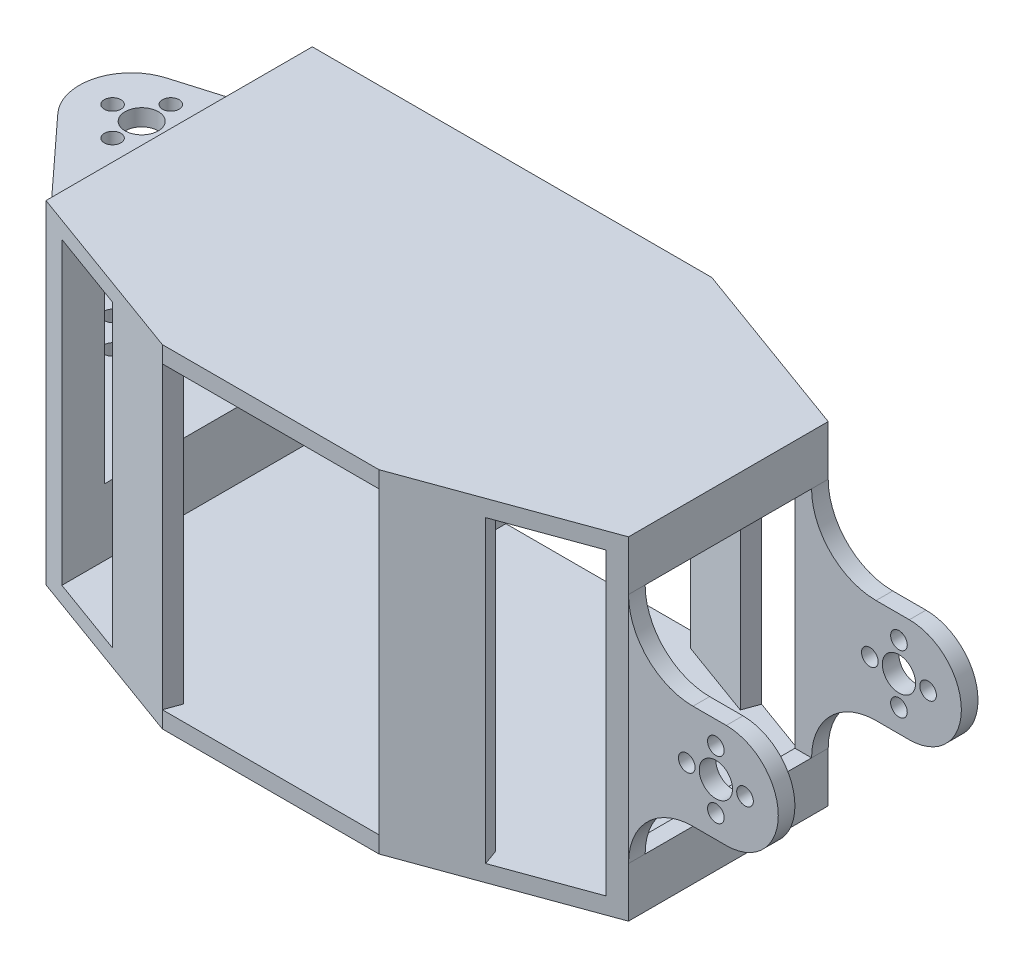
SolidWorks part; units mm, degrees
ref_plane "Alzado" through (0, 0, 0) normal (1, 0, 0) x (0, 1, 0)
ref_plane "Planta" through (0, 0, 0) normal (0, 0, 1) x (0, 1, 0)
ref_plane "Vista lateral" through (0, 0, 0) normal (0, 1, 0) x (-1, 0, 0)
sketch "Croquis2" plane through (0, 0, 0) normal (0, 0, 1) x (0, 1, 0)
  line L1 (-24, 29.7419) -> (24, 29.7419)
  line L2 (-24, 29.7419) -> (-24, -6.2581)
  line L3 (-24, -6.2581) -> (24, -6.2581)
  line L4 (24, 29.7419) -> (24, -6.2581)
  line L5 (-20, 30.4769) -> (20, 30.4769)
  line L6 (-20, 30.4769) -> (-20, -4.2581)
  line L7 (-20, -4.2581) -> (20, -4.2581)
  line L8 (20, 30.4769) -> (20, -4.2581)
  point P8 (0, 29.7419)
  point P9 (0, 30.4769)
  dimension "D1" = 4
  dimension "D2" = 4
  dimension "D3" = 2
  dimension "D4" = 40
  dimension "D5" = 36
  dimension "D6" = 48
extrude "Saliente-Extruir1" add sketch "Croquis2" along normal blind 25 contours L1 L8 L7 L6 L2 L3 L4 region at (-29.1419, -22, 0)
sketch "Croquis3" plane through (0, 24, 0) normal (0, 1, 0) x (-1, 0, 0)
  line L2 (29.7419, 0) -> (-6.2581, 0) construction
  line L3 (29.7419, 12.5) -> (-6.2581, 12.5) construction
  line L4 (29.7419, 25) -> (29.7419, 0) construction
  line L5 (-6.2581, 25) -> (-6.2581, 0) construction
  circle A0 centre (14.7419, 12.5) radius 4
  circle A1 centre (14.7419, 19.5) radius 2
  circle A2 centre (21.7419, 12.5) radius 2
  circle A3 centre (14.7419, 5.5) radius 2
  circle A4 centre (7.7419, 12.5) radius 2
  point P16 (-1.4319, 20)
  dimension "D1" = 8
  dimension "D2" = 4
  dimension "D3" = 7
  dimension "D5" = 15
  dimension "D6" = 12.5
  dimension "D7" = 20
  dimension "D4" = 4
extrude "Cortar-Extruir1" cut sketch "Croquis3" against normal up to surface (48 mm away) up to face at (-11.7419, -24, 12.5)
sketch "Croquis4" plane through (6.2581, 0, 0) normal (1, 0, 0) x (0, 1, 0)
  line L0 (-24, 12.5) -> (24, 12.5) construction
  line L1 (-16, 26.653) -> (16, 26.653)
  line L2 (-16, 26.653) -> (-16, 2.5)
  line L3 (-16, 2.5) -> (16, 2.5)
  line L4 (16, 26.653) -> (16, 2.5)
  line L7 (-24, 25) -> (-24, 0) construction
  line L8 (24, 25) -> (24, 0) construction
  dimension "D1" = 10
  dimension "D2" = 4
  dimension "D3" = 4
extrude "Cortar-Extruir2" cut sketch "Croquis4" against normal blind 40
sketch "Croquis5" plane through (0, 0, 0) normal (0, 0, 1) x (0, 1, 0)
  line L0 (-24, -6.2581) -> (-16, -6.2581) construction
  line L5 (-40, -6.2581) -> (40, -6.2581)
  line L6 (-40, -6.2581) -> (-40, -10.2581)
  line L7 (-36, -12.2581) -> (36, -12.2581)
  line L8 (40, -6.2581) -> (40, -10.2581)
  line L9 (0, 0) -> (0, -130.8301) construction
  line L11 (-40, -10.2581) -> (-40, -146.2581)
  line L13 (-36, -12.2581) -> (-36, -142.2581)
  line L19 (-36, -142.2581) -> (36, -142.2581)
  line L21 (-36, -146.2581) -> (36, -146.2581)
  line L28 (36, -12.2581) -> (36, -142.2581)
  line L30 (40, -10.2581) -> (40, -146.2581)
  line L32 (36, -146.2581) -> (40, -146.2581)
  line L33 (-36, -146.2581) -> (-40, -146.2581)
  point P7 (0, -6.2581)
  dimension "D1" = 6
  dimension "D2" = 80
  dimension "D3" = 4
  dimension "D4" = 130
  dimension "D7" = 4
extrude "Saliente-Extruir3" add sketch "Croquis5" along normal blind 72.5 and the other way blind 7.5 contours L9 L5 L6 L11 L21 L19 L13 L7 | L5 L9 L7 L28 L19 L21 L30 L8 region at (7.8705, 0, 0)
sketch "Croquis8" plane through (6.2581, 0, 0) normal (-1, 0, 0) x (0, -1, 0)
  line L7 (20, 25) -> (20, 0) construction
  line L8 (-20, 2.5) -> (20, 2.5)
  line L9 (-20, 2.5) -> (-20, 64.5)
  line L10 (-20, 64.5) -> (20, 64.5)
  line L11 (20, 2.5) -> (20, 64.5)
  line L12 (-20, 25) -> (-20, 0) construction
  line L13 (40, 72.5) -> (-40, 72.5) construction
  line L15 (40, -7.5) -> (-40, -7.5) construction
  dimension "D1" = 0
  dimension "D2" = 0
  dimension "D3" = 8
  dimension "D4" = 10
extrude "Cortar-Extruir4" cut sketch "Croquis8" against normal blind 10 and the other way blind 10
fillet "Redondeo1" 2 edges at (-29.7419, 22, 25) (-29.7419, 22, 0) type full round first side face at (-11.7419, 22, 25) second side face at (-12.2419, 0, 0) middle face at (-29.7419, 22, 12.5)
fillet "Redondeo2" 2 edges at (-29.7419, -22, 25) (-29.7419, -22, 0) type full round first side face at (-11.7419, -22, 25) second side face at (-9.1169, 0, 0) middle face at (-29.7419, -22, 12.5)
sketch "Croquis9" plane through (146.2581, 0, 0) normal (1, 0, 0) x (0, 1, 0)
  line L0 (-40, 32.5) -> (40, 32.5) construction
  line L1 (-40, -7.5) -> (-40, 72.5) construction
  line L2 (40, -7.5) -> (40, 72.5) construction
  line L4 (-12.5, 56.5) -> (12.5, 56.5)
  line L5 (-12.5, 56.5) -> (-12.5, 52.5)
  line L6 (-12.5, 52.5) -> (12.5, 52.5)
  line L7 (12.5, 56.5) -> (12.5, 52.5)
  point P10 (0, 52.5)
  point P11 (0, 32.5)
  dimension "D1" = 4
  dimension "D2" = 0
  dimension "D3" = 20
  dimension "D4" = 25
extrude "Saliente-Extruir4" add sketch "Croquis9" along normal blind 36
sketch "Croquis10" plane through (0, 0, 56.5) normal (0, 0, 1) x (1, 0, 0)
  line L0 (182.2581, 0) -> (147.8391, 0) construction
  line L1 (182.2581, 12.5) -> (182.2581, -12.5) construction
  circle A0 centre (167.2581, 0) radius 4
  circle A1 centre (167.2581, 7) radius 2
  circle A2 centre (174.2581, 0) radius 2
  circle A3 centre (167.2581, -7) radius 2
  circle A4 centre (160.2581, 0) radius 2
  dimension "D2" = 8
  dimension "D3" = 4
  dimension "D1" = 7
  dimension "D4" = 15
  dimension "D5" = 4
extrude "Cortar-Extruir5" cut sketch "Croquis10" against normal blind 36
fillet "Redondeo3" 2 edges at (182.2581, 12.5, 54.5) (182.2581, -12.5, 54.5) type full round first side face at (164.2581, 12.5, 54.5) second side face at (164.2581, -12.5, 54.5) middle face at (182.2581, 0, 54.5)
ref_plane "Plano1" through (0, 0, 32.5) normal (0, 0, -1) x (0, 1, 0)
mirror "Simetría1" about plane through (0, 0, 32.5) normal (0, 0, -1) of "Redondeo3", "Cortar-Extruir5", "Saliente-Extruir4"
ref_plane "Plano2" through (0, 0, 52.5) normal (0, 0, 1) x (0, -1, 0)
sketch "Croquis11" plane through (146.2581, 0, 0) normal (1, 0, 0) x (0, 1, 0)
  line L0 (-12.5, 52.5) -> (12.5, 52.5) construction
  line L1 (12.5, 12.5) -> (-12.5, 12.5) construction
  line L2 (-40, -7.5) -> (-40, 72.5) construction
  line L3 (-28, 52.5) -> (28, 52.5)
  line L4 (-28, 52.5) -> (-28, 12.5)
  line L5 (-28, 12.5) -> (28, 12.5)
  line L6 (28, 52.5) -> (28, 12.5)
  line L7 (40, -7.5) -> (40, 72.5) construction
  line L8 (-12.5, 52.5) -> (12.5, 52.5) construction
  line L9 (-40, 32.5) -> (40, 32.5) construction
  dimension "D1" = 40
  dimension "D2" = 12
  dimension "D3" = 12
  dimension "D4" = 0
  dimension "D5" = 0
extrude "Cortar-Extruir6" cut sketch "Croquis11" against normal blind 36
sketch "Croquis16" plane through (6.2581, 0, 0) normal (-1, 0, 0) x (0, -1, 0)
  line L0 (20, 25) -> (20, 64.5) construction
  line L1 (-20, 64.5) -> (20, 64.5)
  line L2 (-20, 64.5) -> (-20, 48.5)
  line L3 (-20, 48.5) -> (20, 48.5)
  line L4 (20, 64.5) -> (20, 48.5)
  line L5 (44, 52.5) -> (-44, 52.5) construction
  dimension "D1" = 4
extrude "Saliente-Extruir6" add sketch "Croquis16" against normal blind 6
sketch "Croquis13" plane through (0, -40, 0) normal (0, -1, 0) x (1, 0, 0)
  line L1 (146.2581, 56.5) -> (102.2984, 72.5)
  line L3 (6.2581, 72.5) -> (146.2581, 72.5) construction
  line L4 (44, 52.5) -> (-44, 52.5) construction
  line L5 (102.2984, 72.5) -> (129.9099, 81.6879)
  line L6 (129.9099, 81.6879) -> (158.7193, 75.3016)
  line L7 (158.7193, 75.3016) -> (146.2581, 56.5)
  line L8 (-22, 32.5) -> (22, 32.5) construction
  line L9 (129.9099, -16.6879) -> (158.7193, -10.3016)
  line L10 (102.2984, -7.5) -> (129.9099, -16.6879)
  line L11 (146.2581, 8.5) -> (102.2984, -7.5)
  line L12 (158.7193, -10.3016) -> (146.2581, 8.5)
  line L13 (76.2581, 72.5) -> (76.2581, 2.6393) construction
  line L14 (22.6063, 81.6879) -> (-6.2032, 75.3016)
  line L15 (50.2177, 72.5) -> (22.6063, 81.6879)
  line L16 (6.2581, 56.5) -> (50.2177, 72.5)
  line L17 (-6.2032, 75.3016) -> (6.2581, 56.5)
  point P0 (76.2581, 72.5)
  dimension "D2" = 20
extrude "Cortar-Extruir7" cut sketch "Croquis13" against normal up to surface (80 mm away) up to face at (76.2581, 40, 32.5)
sketch "Croquis17" plane through (35.2677, 0, 96.8972) normal (0.342, 0, 0.9397) x (0.9397, 0, -0.342)
  line L0 (71.3326, -36) -> (113.8568, -36) construction
  line L1 (71.3326, 36) -> (91.3326, 36)
  line L2 (71.3326, 36) -> (71.3326, -36)
  line L3 (71.3326, -36) -> (91.3326, -36)
  line L4 (91.3326, 36) -> (91.3326, -36)
  dimension "D1" = 20
extrude "Saliente-Extruir7" add sketch "Croquis17" against normal blind 4
mirror "Simetría2" about plane through (0, 0, 32.5) normal (0, 0, -1) of "Saliente-Extruir7"
sketch "Croquis18" plane through (0, -24, 0) normal (0, -1, 0) x (1, 0, 0)
  line L2 (6.2581, 0) -> (6.2581, -2.5785)
  line L3 (6.2581, 56.5) -> (-26.4404, 20.9639)
  line L4 (-26.4404, 20.9639) -> (6.2581, 25)
  line L5 (6.2581, 25) -> (6.2581, 56.5)
  line L7 (6.2581, -7.5) -> (6.2581, -2.5785)
  line L8 (6.2581, -7.5) -> (-20.793, 0.515)
  line L9 (-17.2419, 0) -> (6.2581, 0)
  arc A0 (-17.2419, 25) -> (-17.2419, 0) centre (-17.2419, 12.5) ccw construction
  arc A2 (-20.793, 0.515) -> (-17.2419, 0) centre (-17.2419, 12.5) ccw
extrude "Saliente-Extruir8" add sketch "Croquis18" against normal blind 4
mirror "Simetría3" about plane through (0, 0, 0) normal (0, 1, 0) of "Saliente-Extruir8"
sketch "Croquis20" plane through (-17.4267, 0, 47.8795) normal (-0.342, 0, 0.9397) x (0.9397, 0, 0.342)
  line L0 (31.5899, -36) -> (71.9857, -36) construction
  line L1 (71.9857, 36) -> (51.9857, 36)
  line L2 (71.9857, 36) -> (71.9857, -36)
  line L3 (71.9857, -36) -> (51.9857, -36)
  line L4 (51.9857, 36) -> (51.9857, -36)
  dimension "D1" = 20
ref_plane "Plano3" through (6.2581, -20, 0) normal (0, 1, 0) x (-1, 0, 0)
sketch "Croquis23" plane through (0, 0, 0) normal (0, 0, -1) x (1, 0, 0)
  line L0 (-4.7419, 20) -> (17.2581, 20) construction
  line L1 (6.2581, -20) -> (-1.5045, -20)
  line L2 (6.2581, -20) -> (6.2581, 20)
  line L3 (6.2581, 20) -> (-1.5045, 20)
  line L4 (-1.5045, -20) -> (-1.5045, 20)
extrude "Cortar-Extruir8" cut sketch "Croquis23" against normal blind 10
extrude "Saliente-Extruir9" add sketch "Croquis20" against normal blind 4 contours L2 L3 L4 L1
fillet "Redondeo4" radius 15.5 4 edges at (146.2581, -12.5, 10.5) (146.2581, 12.5, 10.5) (146.2581, 12.5, 54.5) (146.2581, -12.5, 54.5)
sketch "Croquis24" plane through (0, 0, -7.5) normal (0, 0, -1) x (1, 0, 0)
  line L0 (12.2581, -36) -> (102.2984, -36) construction
  line L1 (32.7919, 36) -> (52.7919, 36)
  line L2 (32.7919, 36) -> (32.7919, -36)
  line L3 (32.7919, -36) -> (52.7919, -36)
  line L4 (52.7919, 36) -> (52.7919, -36)
  dimension "D1" = 20
extrude "Saliente-Extruir10" add sketch "Croquis24" against normal blind 4
